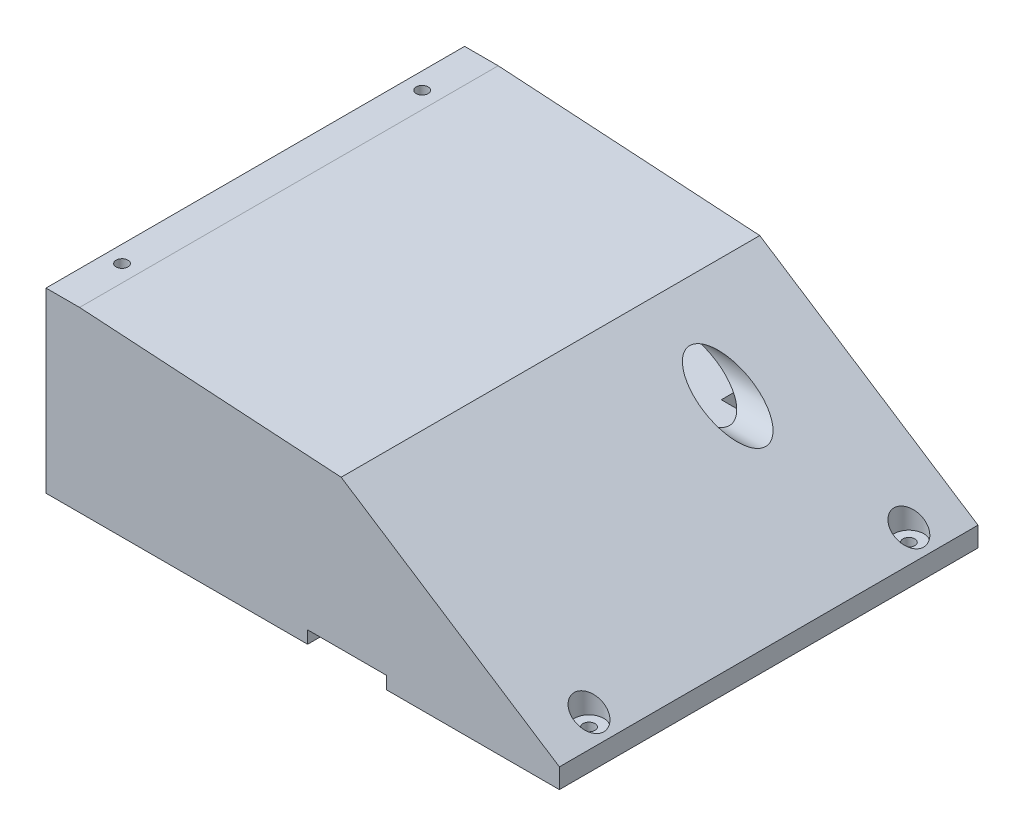
SolidWorks part; units mm, degrees
ref_plane "Front Plane" through (0, 0, 0) normal (0, 0, 1) x (1, 0, 0)
ref_plane "Top Plane" through (0, 0, 0) normal (0, 1, 0) x (1, 0, 0)
ref_plane "Right Plane" through (0, 0, 0) normal (1, 0, 0) x (0, 0, -1)
sketch "Sketch1" plane through (0, 0, 0) normal (0, 0, 1) x (1, 0, 0)
  line L0 (0, 0) -> (-20, 0)
  line L3 (-242.9846, 20) -> (-242.9846, 25)
  line L4 (-242.9846, 25) -> (-260, 25)
  line L5 (-260, 25) -> (-260, 30)
  line L10 (-242.9846, 85) -> (-260, 85)
  line L11 (-260, 85) -> (-260, 90)
  line L14 (-242.9846, 90) -> (-260, 90)
  line L23 (-49.1581, 30) -> (-260, 30)
  line L26 (-49.1581, 30) -> (-122.3017, 77.5)
  line L27 (-260, 30) -> (-120, 30) construction
  line L28 (-260, 30) -> (-260, 67) construction
  line L29 (-260, 67) -> (-120, 67) construction
  line L30 (-120, 30) -> (-120, 67) construction
  line L31 (-110.512, 81.7673) -> (0, 10)
  line L32 (-20, 0) -> (-20, 20)
  line L35 (0, 0) -> (0, 10)
  line L36 (-242.9846, 20) -> (-20, 20)
  line L37 (-242.9846, 85) -> (-122.3017, 77.5)
  line L38 (-242.9846, 90) -> (-110.512, 81.7673)
  dimension "D1" = 20
  dimension "D2" = 20
  dimension "D3" = 10
  dimension "D4" = 55
  dimension "D5" = 5
  dimension "D6" = 140
  dimension "D7" = 37
  dimension "D9" = 33
  dimension "D10" = 10
  dimension "D11" = 260
  dimension "D13" = 222.9846
extrude "Boss-Extrude1" add sketch "Sketch1" along normal blind 212
sketch "Sketch2" plane through (0, 0, 0) normal (0, 0, -1) x (-1, 0, 0)
  line L2 (0, 0) -> (260, 0)
  line L3 (260, 0) -> (260, 90)
  line L5 (110.512, 81.7673) -> (0, 10)
  line L6 (0, 10) -> (0, 0)
  line L7 (260, 90) -> (110.512, 81.7673)
extrude "Boss-Extrude2" add sketch "Sketch2" against normal blind 10
sketch "Sketch3" plane through (0, 0, 212) normal (0, 0, 1) x (1, 0, 0)
  line L1 (-110.512, 81.7673) -> (0, 10)
  line L2 (0, 10) -> (0, 0)
  line L3 (0, 0) -> (-260, 0)
  line L4 (-260, 0) -> (-260, 90)
  line L5 (-260, 90) -> (-110.512, 81.7673)
extrude "Boss-Extrude3" add sketch "Sketch3" against normal blind 10
sketch "Sketch4" plane through (0, 0, 0) normal (0, -1, 0) x (1, 0, 0)
  line L0 (0, 212) -> (0, 0) construction
  line L4 (-260, 212) -> (0, 212) construction
  line L5 (0, 106) -> (-20, 106) construction
  line L6 (-20, 202) -> (-20, 10) construction
  circle A0 centre (-10, 187) radius 3
  circle A1 centre (-10, 25) radius 3
  dimension "D1" = 6
  dimension "D2" = 10
  dimension "D3" = 25
extrude "Cut-Extrude1" cut sketch "Sketch4" against normal through all
ref_plane "Plane1" through (0, 10, 0) normal (0, -1, 0) x (-1, 0, 0)
sketch "Sketch6" plane through (0, 10, 0) normal (0, -1, 0) x (-1, 0, 0)
  line L0 (0, -106) -> (20, -106) construction
  line L1 (0, -212) -> (0, 0) construction
  line L2 (20, -202) -> (20, -10) construction
  circle A0 centre (10, -25) radius 7.5
  circle A1 centre (10, -187) radius 7.5
  dimension "D1" = 15
extrude "Cut-Extrude2" cut sketch "Sketch6" against normal through all
sketch "Sketch7" plane through (0, 20, 0) normal (0, -1, 0) x (1, 0, 0)
  line L0 (-242.9846, 106) -> (-102.9846, 106) construction
  line L1 (-242.9846, 202) -> (-242.9846, 10) construction
  line L2 (-242.9846, 166) -> (-102.9846, 166) construction
  line L3 (-242.9846, 166) -> (-242.9846, 46) construction
  line L4 (-242.9846, 46) -> (-102.9846, 46) construction
  line L5 (-102.9846, 166) -> (-102.9846, 46) construction
  line L7 (-20, 10) -> (-260, 10) construction
  line L8 (-260, 202) -> (-20, 202) construction
  line L9 (-97.0991, 166) -> (-87.0991, 166)
  line L10 (-97.0991, 166) -> (-97.0991, 46)
  line L11 (-97.0991, 46) -> (-87.0991, 46)
  line L12 (-87.0991, 166) -> (-87.0991, 46)
  line L13 (-100, 30) -> (-40, 30)
  line L14 (-100, 30) -> (-100, 15)
  line L15 (-100, 15) -> (-40, 15)
  line L16 (-40, 30) -> (-40, 15)
  line L17 (-20, 202) -> (-20, 10) construction
  circle A0 centre (-161.4846, 161) radius 1.5
  circle A1 centre (-225.6846, 161) radius 1.5
  circle A2 centre (-161.4846, 51) radius 1.5
  circle A3 centre (-225.6846, 51) radius 1.5
  circle A4 centre (-67.9846, 136) radius 12.5
  dimension "D4" = 3
  dimension "D6" = 3
  dimension "D9" = 25
  dimension "D1" = 120
  dimension "D2" = 140
  dimension "D3" = 36
  dimension "D5" = 58.5
  dimension "D7" = 122.7
  dimension "D8" = 5
  dimension "D10" = 30
  dimension "D11" = 35
  dimension "D12" = 10
  dimension "D13" = 120
  dimension "D14" = 15
  dimension "D15" = 60
  dimension "D16" = 5
  dimension "D17" = 20
extrude "Cut-Extrude3" cut sketch "Sketch7" against normal blind 12.5
ref_plane "Plane2" through (-110.512, 0, 0) normal (-1, 0, 0) x (0, 0, 1)
sketch "Sketch8" plane through (-110.512, 0, 0) normal (-1, 0, 0) x (0, 0, 1)
  line L0 (202, 30) -> (30, 30) construction
  circle A0 centre (54, 57.25) radius 12.5
  point P4 (116, 30)
  dimension "D3" = 25
  dimension "D1" = 27.25
  dimension "D2" = 62
extrude "Cut-Extrude4" cut sketch "Sketch8" against normal up to next
sketch "Sketch9" plane through (0, 25, 0) normal (0, -1, 0) x (1, 0, 0)
  line L0 (-242.9846, 202) -> (-260, 202) construction
  line L1 (-260, 202) -> (-260, 10) construction
  line L2 (-242.9846, 106) -> (-260, 106) construction
  line L3 (-242.9846, 202) -> (-242.9846, 10) construction
  circle A0 centre (-251.5, 182) radius 3
  circle A1 centre (-251.5, 30) radius 3
  dimension "D1" = 20
  dimension "D3" = 6
  dimension "D2" = 8.5
extrude "Cut-Extrude5" cut sketch "Sketch9" against normal through all both and the other way through all
sketch "Sketch10" plane through (0, 0, 212) normal (0, 0, 1) x (1, 0, 0)
  line L0 (-260, 0) -> (0, 0) construction
  line L1 (-127.5, 0) -> (-87.5, 0)
  line L2 (-127.5, 0) -> (-127.5, 6.35)
  line L3 (-127.5, 6.35) -> (-87.5, 6.35)
  line L4 (-87.5, 0) -> (-87.5, 6.35)
  line L5 (0, 0) -> (0, 10) construction
  dimension "D1" = 87.5
  dimension "D2" = 40
  dimension "D3" = 6.35
extrude "Cut-Extrude6" cut sketch "Sketch10" against normal through all both
